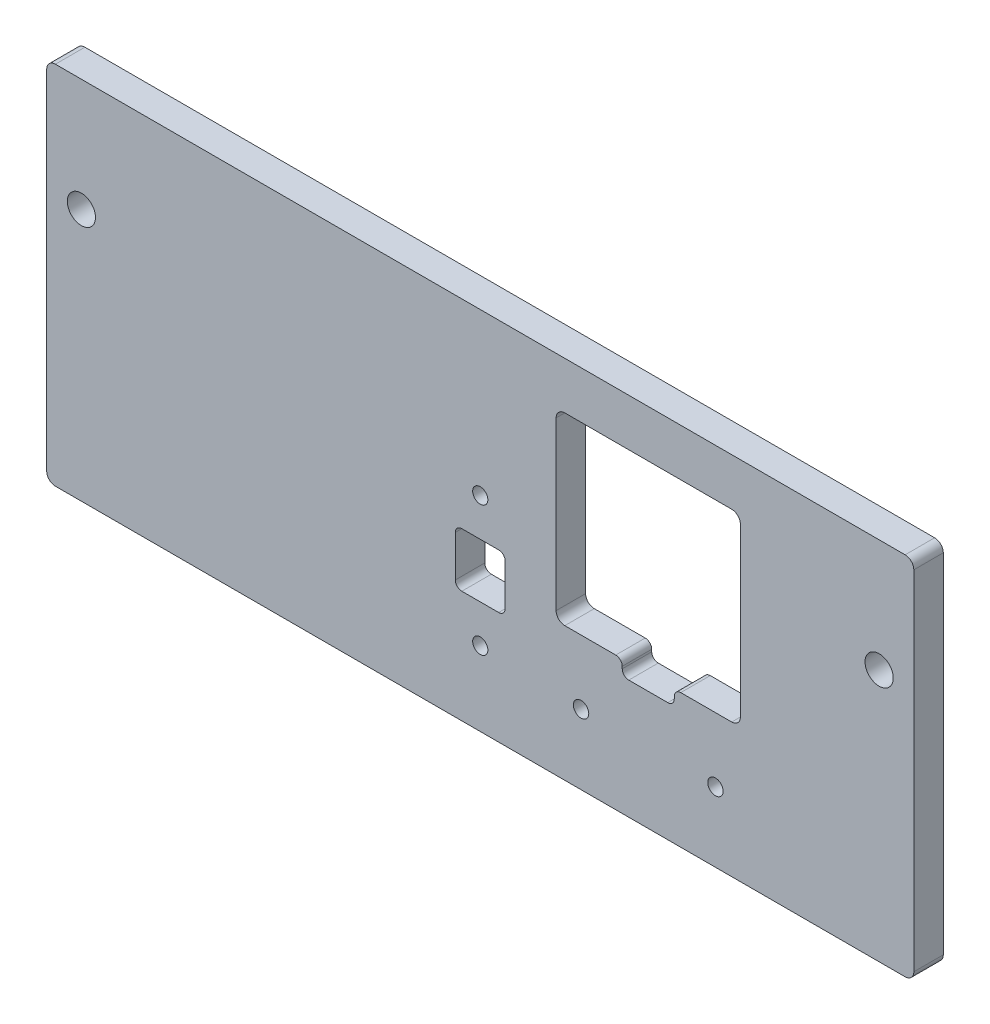
SolidWorks part; units mm, degrees
ref_plane "Front Plane" through (0, 0, 0) normal (0, 0, 1) x (1, 0, 0)
ref_plane "Top Plane" through (0, 0, 0) normal (0, 1, 0) x (1, 0, 0)
ref_plane "Right Plane" through (0, 0, 0) normal (1, 0, 0) x (0, 0, -1)
sketch "Sketch1" plane through (0, 0, 0) normal (0, 0, 1) x (1, 0, 0)
  line L1 (100, -42.15) -> (-100, -42.15)
  line L2 (100, -42.15) -> (100, 42.15)
  line L3 (100, 42.15) -> (-100, 42.15)
  line L4 (-100, -42.15) -> (-100, 42.15)
  line L5 (100, -42.15) -> (-100, 42.15) construction
  line L6 (100, 42.15) -> (-100, -42.15) construction
  point P0 (0, 0)
  dimension "D1" = 200
  dimension "D2" = 84.3
extrude "Boss-Extrude1" add sketch "Sketch1" along normal blind 6.8
sketch "Sketch2" plane through (0, 0, 6.8) normal (0, 0, 1) x (1, 0, 0)
  line L0 (100, 42.15) -> (-100, 42.15) construction
  line L1 (92, 16.15) -> (-92, 16.15) construction
  circle A0 centre (-92, 16.15) radius 3.25
  circle A1 centre (92, 16.15) radius 3.25
  point P10 (0, 16.15)
  dimension "D1" = 6.5
  dimension "D2" = 92
  dimension "D3" = 26
extrude "Cut-Extrude1" cut sketch "Sketch2" against normal blind 6.8
fillet "Fillet1" radius 2 4 edges at (100, 42.15, 3.4) (100, -42.15, 3.4) (-100, -42.15, 3.4) (-100, 42.15, 3.4)
sketch "Sketch3" plane through (0, 0, 6.8) normal (0, 0, 1) x (1, 0, 0)
  line L0 (100, -40.15) -> (100, 40.15) construction
  line L1 (60, -11.25) -> (17.5, -11.25)
  line L2 (60, -11.25) -> (60, 31.25)
  line L3 (60, 31.25) -> (17.5, 31.25)
  line L4 (17.5, -11.25) -> (17.5, 31.25)
  line L5 (60, -11.25) -> (17.5, 31.25) construction
  line L6 (60, 31.25) -> (17.5, -11.25) construction
  line L7 (54.25, -26.082) -> (23.25, -26.082) construction
  circle A0 centre (23.25, -26.082) radius 1.775
  circle A1 centre (54.25, -26.082) radius 1.775
  point P0 (38.75, 10)
  point P16 (38.75, -26.082)
  dimension "D6" = 3.55
  dimension "D1" = 42.5
  dimension "D2" = 40
  dimension "D3" = 10
  dimension "D4" = 14.832
  dimension "D5" = 31
extrude "Cut-Extrude2" cut sketch "Sketch3" against normal through all
fillet "Fillet2" radius 2 4 edges at (60, 31.25, 3.4) (17.5, 31.25, 3.4) (17.5, -11.25, 3.4) (60, -11.25, 3.4)
mirror "Mirror1" [suppressed] about plane through (0, 0, 0) normal (1, 0, 0)
sketch "Sketch4" plane through (0, 0, 6.8) normal (0, 0, 1) x (1, 0, 0)
  line L1 (44.75, -14.75) -> (32.75, -14.75)
  line L2 (44.75, -14.75) -> (44.75, -7.75)
  line L3 (44.75, -7.75) -> (32.75, -7.75)
  line L4 (32.75, -14.75) -> (32.75, -7.75)
  line L5 (44.75, -14.75) -> (32.75, -7.75) construction
  line L6 (44.75, -7.75) -> (32.75, -14.75) construction
  line L7 (19.5, -11.25) -> (58, -11.25) construction
  point P0 (38.75, -11.25)
  dimension "D1" = 3.5
  dimension "D2" = 12
extrude "Cut-Extrude3" cut sketch "Sketch4" against normal through all
fillet "Fillet3" radius 1.5 4 edges at (44.75, -14.75, 3.4) (32.75, -14.75, 3.4) (32.75, -11.25, 3.4) (44.75, -11.25, 3.4)
sketch "Sketch5" plane through (0, 0, 6.8) normal (0, 0, 1) x (1, 0, 0)
  line L0 (0, 5) -> (0, -25) construction
  line L1 (5.75, -16.25) -> (-5.75, -16.25)
  line L2 (5.75, -16.25) -> (5.75, -3.75)
  line L3 (5.75, -3.75) -> (-5.75, -3.75)
  line L4 (-5.75, -16.25) -> (-5.75, -3.75)
  line L5 (5.75, -16.25) -> (-5.75, -3.75) construction
  line L6 (5.75, -3.75) -> (-5.75, -16.25) construction
  circle A0 centre (0, -25) radius 1.75
  circle A1 centre (0, 5) radius 1.75
  point P0 (0, -10)
  point P10 (0, -10)
  dimension "D4" = 3.5
  dimension "D1" = 12.5
  dimension "D2" = 11.5
  dimension "D3" = 30
  dimension "D5" = 10
extrude "Cut-Extrude4" cut sketch "Sketch5" against normal through all
fillet "Fillet4" radius 1.5 4 edges at (-5.75, -3.75, 3.4) (5.75, -3.75, 3.4) (5.75, -16.25, 3.4) (-5.75, -16.25, 3.4)
